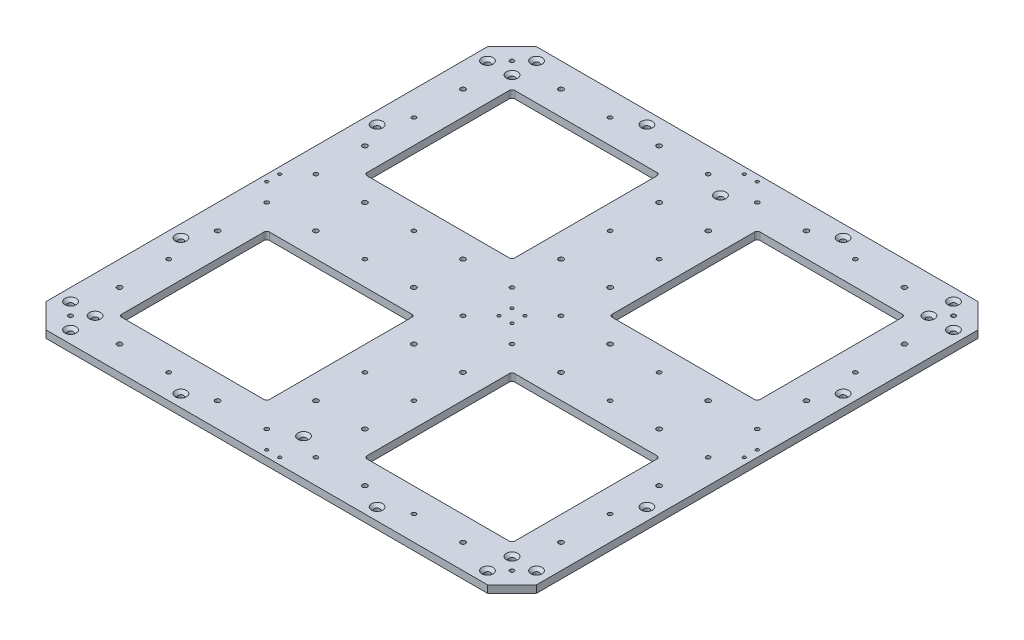
SolidWorks part; units mm, degrees
ref_plane "Front Plane" through (0, 0, 0) normal (0, 0, 1) x (1, 0, 0)
ref_plane "Top Plane" through (0, 0, 0) normal (0, 1, 0) x (1, 0, 0)
ref_plane "Right Plane" through (0, 0, 0) normal (1, 0, 0) x (0, 0, -1)
sketch "Sketch1" plane through (0, 0, 0) normal (0, 1, 0) x (1, 0, 0)
  line L0 (-400, 360) -> (-400, -360)
  line L1 (-400, -360) -> (-360, -400)
  line L2 (-360, -400) -> (360, -400)
  line L3 (360, -400) -> (400, -360)
  line L4 (400, -360) -> (400, 360)
  line L5 (400, 360) -> (360, 400)
  line L6 (360, 400) -> (-360, 400)
  line L7 (-360, 400) -> (-400, 360)
  line L8 (0, 400) -> (0, -400) construction
  line L9 (-400, 0) -> (400, 0) construction
  line L10 (-400, 360) -> (400, 360) construction
  line L11 (-400, -360) -> (400, -360) construction
  line L12 (-360, 400) -> (-360, -400) construction
  line L13 (360, -400) -> (360, 400) construction
  line L14 (-320.5, -79.5) -> (-320.5, 320.5) construction
  line L15 (-320.5, 320.5) -> (79.5, 320.5) construction
  line L16 (79.5, 79.5) -> (-320.5, 79.5) construction
  line L19 (-320.5, -79.5) -> (-79.5, -79.5)
  line L20 (-320.5, -79.5) -> (-320.5, -320.5)
  line L21 (-320.5, -320.5) -> (-79.5, -320.5)
  line L22 (-79.5, -79.5) -> (-79.5, -320.5)
  line L23 (79.5, 320.5) -> (320.5, 320.5)
  line L24 (79.5, 320.5) -> (79.5, 79.5)
  line L25 (79.5, 79.5) -> (320.5, 79.5)
  line L26 (320.5, 320.5) -> (320.5, 79.5)
  line L27 (79.5, -79.5) -> (320.5, -79.5)
  line L28 (79.5, -79.5) -> (79.5, -320.5)
  line L29 (79.5, -320.5) -> (320.5, -320.5)
  line L30 (320.5, -79.5) -> (320.5, -320.5)
  line L31 (-320.5, 320.5) -> (-79.5, 320.5)
  line L32 (-79.5, -320.5) -> (79.5, -320.5) construction
  line L33 (320.5, 79.5) -> (320.5, -79.5) construction
  line L34 (-320.5, 320.5) -> (-320.5, 79.5)
  line L35 (-320.5, 79.5) -> (-79.5, 79.5)
  line L36 (79.5, -79.5) -> (-79.5, -79.5) construction
  line L37 (79.5, 79.5) -> (79.5, -79.5) construction
  line L38 (-79.5, 320.5) -> (-79.5, 79.5)
  dimension "D1" = 800
  dimension "D2" = 800
  dimension "D3" = 40
  dimension "D4" = 79.5
  dimension "D5" = 79.5
  dimension "D6" = 79.5
  dimension "D7" = 79.5
  dimension "D8" = 79.5
  dimension "D9" = 79.5
  dimension "D10" = 79.5
  dimension "D11" = 79.5
extrude "Boss-Extrude1" add sketch "Sketch1" along normal blind 12
sketch "Sketch2" plane through (0, 12, 0) normal (0, 1, 0) x (1, 0, 0)
  line L0 (-400, 200) -> (-200, 200) construction
  line L1 (-400, 360) -> (-400, -360) construction
  line L2 (-200, 200) -> (-200, 400) construction
  line L3 (360, 400) -> (-360, 400) construction
  line L4 (-246.669, 153.331) -> (-153.331, 246.669) construction
  line L5 (-246.669, 246.669) -> (-153.331, 246.669) construction
  line L6 (-246.669, 246.669) -> (-246.669, 153.331) construction
  line L7 (-246.669, 153.331) -> (-153.331, 153.331) construction
  line L8 (-153.331, 246.669) -> (-153.331, 153.331) construction
  line L9 (-260, 210) -> (-140, 210) construction
  line L10 (-200, 200) -> (-200, 210) construction
  circle A0 centre (-200, 200) radius 74.5 construction
  circle A1 centre (-246.669, 153.331) radius 4.25
  circle A2 centre (-153.331, 153.331) radius 4.25
  circle A3 centre (-153.331, 246.669) radius 4.25
  circle A4 centre (-246.669, 246.669) radius 4.25
  circle A5 centre (-260, 210) radius 4
  circle A6 centre (-140, 210) radius 4
  dimension "D3" = 149
  dimension "D5" = 8.5
  dimension "D8" = 8
  dimension "D1" = 200
  dimension "D2" = 200
  dimension "D4" = 132
  dimension "D6" = 10
  dimension "D7" = 120
extrude "Cut-Extrude1" [suppressed] cut sketch "Sketch2" against normal through all
hole_wizard "M8 Tapped Hole1" positions "Sketch5" profile "Sketch6" tap size "M8" standard "ISO" end condition through all
sketch "Sketch5" plane through (0, 12, 0) normal (0, 1, 0) x (1, 0, 0)
  line L0 (-400, 360) -> (400, 360) construction
  line L2 (-360, 400) -> (-360, -400) construction
  line L4 (-400, -360) -> (400, -360) construction
  line L6 (360, -400) -> (360, 400) construction
  line L8 (-400, 0) -> (400, 0) construction
  line L9 (-400, 360) -> (-400, -360) construction
  line L10 (400, -360) -> (400, 360) construction
  line L12 (0, 400) -> (0, -400) construction
  line L13 (360, 400) -> (-360, 400) construction
  line L14 (-360, -400) -> (360, -400) construction
  line L16 (-400, -40) -> (400, -40) construction
  line L17 (-40, 400) -> (-40, -400) construction
  line L18 (-400, 40) -> (400, 40) construction
  line L19 (40, 400) -> (40, -400) construction
  line L21 (-200, 400) -> (-200, -400) construction
  line L22 (-400, -200) -> (400, -200) construction
  line L23 (200, 400) -> (200, -400) construction
  line L24 (-400, 200) -> (400, 200) construction
  point P47 (-360, 360)
  point P49 (360, 360)
  point P51 (-40, 360)
  point P53 (40, 360)
  point P55 (-40, 40)
  point P57 (40, 40)
  point P59 (360, 40)
  point P61 (-360, 40)
  point P63 (-360, -40)
  point P65 (-360, -360)
  point P67 (-40, -40)
  point P69 (-40, -360)
  point P71 (40, -360)
  point P73 (360, -360)
  point P75 (360, -40)
  point P77 (40, -40)
  point P90 (-200, 360)
  point P92 (200, 360)
  point P94 (360, 200)
  point P96 (200, 40)
  point P98 (40, 200)
  point P100 (-40, 200)
  point P102 (-200, 40)
  point P104 (-360, 200)
  point P106 (-200, -40)
  point P108 (-360, -200)
  point P110 (-200, -360)
  point P112 (-40, -200)
  point P114 (40, -200)
  point P116 (200, -40)
  point P118 (360, -200)
  point P120 (200, -360)
  dimension "D1" = 40
  dimension "D2" = 40
  dimension "D3" = 200
  dimension "D4" = 200
sketch "Sketch6" plane through (-360, 12, -360) normal (1, 0, 0) x (0, 0, 1)
  line L0 (0, 0) -> (0, 12)
  line L1 (0, 12) -> (3.4, 12)
  line L2 (3.4, 12) -> (3.4, 0)
  line L5 (3.4, 0) -> (0, 0)
  line L11 (0, -6.35) -> (0, 107.95) construction
  dimension "Thru Tap Drill Dia." = 6.8
  dimension "Thru Tap Drill Depth" = 12
cosmetic thread "Hole Thread1" parameters "D2"=8
cosmetic thread "Hole Thread2" parameters "D2"=8
cosmetic thread "Hole Thread3" parameters "D2"=8
cosmetic thread "Hole Thread4" parameters "D2"=8
cosmetic thread "Hole Thread5" parameters "D2"=8
cosmetic thread "Hole Thread6" parameters "D2"=8
cosmetic thread "Hole Thread7" parameters "D2"=8
cosmetic thread "Hole Thread8" parameters "D2"=8
cosmetic thread "Hole Thread9" parameters "D2"=8
cosmetic thread "Hole Thread10" parameters "D2"=8
cosmetic thread "Hole Thread11" parameters "D2"=8
cosmetic thread "Hole Thread12" parameters "D2"=8
cosmetic thread "Hole Thread13" parameters "D2"=8
cosmetic thread "Hole Thread14" parameters "D2"=8
cosmetic thread "Hole Thread15" parameters "D2"=8
cosmetic thread "Hole Thread16" parameters "D2"=8
cosmetic thread "Hole Thread17" parameters "D2"=8
cosmetic thread "Hole Thread18" parameters "D2"=8
cosmetic thread "Hole Thread19" parameters "D2"=8
cosmetic thread "Hole Thread20" parameters "D2"=8
cosmetic thread "Hole Thread21" parameters "D2"=8
cosmetic thread "Hole Thread22" parameters "D2"=8
cosmetic thread "Hole Thread23" parameters "D2"=8
cosmetic thread "Hole Thread24" parameters "D2"=8
cosmetic thread "Hole Thread25" parameters "D2"=8
cosmetic thread "Hole Thread26" parameters "D2"=8
cosmetic thread "Hole Thread27" parameters "D2"=8
cosmetic thread "Hole Thread28" parameters "D2"=8
cosmetic thread "Hole Thread29" parameters "D2"=8
cosmetic thread "Hole Thread30" parameters "D2"=8
cosmetic thread "Hole Thread31" parameters "D2"=8
cosmetic thread "Hole Thread32" parameters "D2"=8
hole_wizard "Ø8.0mm Dowel Hole1" positions "Sketch8" profile "Sketch7" hole size "Ø8.0" standard "ANSI Metric" end condition through all
sketch "Sketch8" plane through (0, 12, 0) normal (0, 1, 0) x (1, 0, 0)
  line L0 (-360, 360) -> (-200, 360) construction
  line L1 (-200, 360) -> (-40, 360) construction
  line L2 (-40, 360) -> (-40, 200) construction
  line L3 (-40, 200) -> (-40, 40) construction
  line L4 (-40, 40) -> (-200, 40) construction
  line L5 (-200, 40) -> (-360, 40) construction
  line L6 (-360, 40) -> (-360, 200) construction
  line L7 (-360, 200) -> (-360, 360) construction
  point P0 (-280, 360)
  point P2 (-120, 360)
  point P4 (-40, 280)
  point P6 (-40, 120)
  point P8 (-120, 40)
  point P10 (-280, 40)
  point P12 (-360, 120)
  point P14 (-360, 280)
sketch "Sketch7" plane through (-280, 12, -360) normal (1, 0, 0) x (0, 0, 1)
  line L0 (0, 0) -> (0, 12)
  line L1 (0, 12) -> (4, 12)
  line L2 (4, 12) -> (4, 0)
  line L5 (4, 0) -> (0, 0)
  line L11 (0, -6.35) -> (0, 107.95) construction
  dimension "Thru Hole Dia." = 8
  dimension "Thru Hole Depth" = 12
pattern_linear "LPattern1" count 2 spacing 400 along (1, 0, 0) count 2 spacing 400 along (0, 0, 1) of "Ø8.0mm Dowel Hole1"
hole_wizard "CSK for M8 Hex Socket Countersunk Head Screw1" positions "Sketch10" profile "Sketch9" countersink size "M8" standard "DIN" end condition through all
sketch "Sketch10" plane through (0, 12, 0) normal (0, 1, 0) x (1, 0, 0)
  line L0 (-380, 340) -> (-380, -340) construction
  line L1 (-380, -340) -> (380, -340) construction
  line L2 (380, -340) -> (380, 340) construction
  line L3 (380, 340) -> (-380, 340) construction
  line L5 (-340, 380) -> (-340, -380) construction
  line L6 (-340, -380) -> (340, -380) construction
  line L7 (340, -380) -> (340, 380) construction
  line L8 (340, 380) -> (-340, 380) construction
  line L10 (360, 400) -> (-360, 400) construction
  line L11 (-400, 360) -> (-400, -360) construction
  line L12 (400, -360) -> (400, 360) construction
  line L13 (-360, -400) -> (360, -400) construction
  line L14 (-160, 380) -> (-160, -380) construction
  line L16 (-380, 160) -> (380, 160) construction
  line L18 (-380, -160) -> (380, -160) construction
  line L20 (160, 380) -> (160, -380) construction
  point P0 (-380, 340)
  point P2 (-340, 380)
  point P6 (-380, -340)
  point P8 (380, -340)
  point P10 (380, 340)
  point P16 (-340, -380)
  point P17 (340, -380)
  point P19 (340, 380)
  point P52 (340, 340)
  point P54 (340, -340)
  point P56 (-340, -340)
  point P58 (0, -340)
  point P60 (0, 340)
  point P62 (-340, 340)
  point P64 (-160, 380)
  point P68 (160, 380)
  point P72 (380, 160)
  point P78 (380, -160)
  point P80 (160, -380)
  point P84 (-160, -380)
  point P88 (-380, -160)
  point P90 (-380, 160)
  dimension "D1" = 60
  dimension "D2" = 60
  dimension "D3" = 60
  dimension "D4" = 20
  dimension "D5" = 60
  dimension "D6" = 20
  dimension "D7" = 20
  dimension "D8" = 20
  dimension "D9" = 180
  dimension "D10" = 180
  dimension "D11" = 180
  dimension "D12" = 180
sketch "Sketch9" plane through (-380, 12, -340) normal (1, 0, 0) x (0, 0, 1)
  line L0 (0, 0) -> (0, 12)
  line L1 (0, 12) -> (4.5, 12)
  line L2 (4.5, 12) -> (4.5, 4.625)
  line L3 (4.5, 4.625) -> (9.125, 0)
  line L5 (9.125, 0) -> (0, 0)
  line L6 (-4.5, 4.625) -> (-9.125, 0) construction
  line L11 (0, -6.35) -> (0, 107.95) construction
  dimension "Thru Hole Dia." = 9
  dimension "Thru Hole Depth" = 12
  dimension "Near C'Sink Dia." = 18.25
  dimension "Near C'Sink Angle" = 90
fillet "Fillet1" radius 4.5 16 edges at (320.5, 6, -320.5) (-79.5, 6, 79.5) (320.5, 6, 79.5) (320.5, 6, -79.5) (320.5, 6, 320.5) (-79.5, 6, 320.5) (-320.5, 6, 79.5) (79.5, 6, 79.5) (79.5, 6, -320.5) (79.5, 6, -79.5) (79.5, 6, 320.5) (-320.5, 6, 320.5) (-320.5, 6, -79.5) (-79.5, 6, -79.5) (-79.5, 6, -320.5) (-320.5, 6, -320.5)
hole_wizard "M6 Tapped Hole1" positions "Sketch13" profile "Sketch12" tap size "M6" standard "ISO" end condition through all
sketch "Sketch13" plane through (0, 12, 0) normal (0, 1, 0) x (1, 0, 0)
  line L0 (0, 0) -> (-40, 0) construction
  line L1 (-40, 0) -> (0, 40) construction
  line L2 (0, 40) -> (0, 0) construction
  line L3 (0, 0) -> (0, -40) construction
  line L4 (0, -40) -> (-40, 0) construction
  line L6 (0, 0) -> (-20, -20) construction
  line L8 (0, 0) -> (-20, 20) construction
  line L9 (-400, 0) -> (-400, 40) construction
  line L11 (-400, 40) -> (-360, 0) construction
  line L12 (-360, 0) -> (-400, 0) construction
  line L13 (-400, 0) -> (-400, -40) construction
  line L14 (-400, -40) -> (-360, 0) construction
  line L16 (-400, 0) -> (-380, 20) construction
  line L18 (-400, 0) -> (-380, -20) construction
  line L19 (-400, 40) -> (0, 40) construction
  line L21 (-400, -40) -> (0, -40) construction
  line L22 (0, 0) -> (-360, 0) construction
  point P26 (-10.6066, 10.6066)
  point P28 (-10.6066, -10.6066)
  point P63 (-389.3934, 10.6066)
  point P65 (-389.3934, -10.6066)
  dimension "D1" = 40
  dimension "D2" = 40
  dimension "D3" = 15
  dimension "D4" = 15
  dimension "D5" = 400
  dimension "D6" = 15
  dimension "D7" = 15
sketch "Sketch12" plane through (-10.6066, 12, -10.6066) normal (1, 0, 0) x (0, 0, 1)
  line L0 (0, 0) -> (0, 12)
  line L1 (0, 12) -> (2.5, 12)
  line L2 (2.5, 12) -> (2.5, 0)
  line L5 (2.5, 0) -> (0, 0)
  line L11 (0, -6.35) -> (0, 107.95) construction
  dimension "Thru Tap Drill Dia." = 5
  dimension "Thru Tap Drill Depth" = 12
cosmetic thread "Hole Thread33" parameters "D2"=6
cosmetic thread "Hole Thread34" parameters "D2"=6
cosmetic thread "Hole Thread35" parameters "D2"=6
cosmetic thread "Hole Thread36" parameters "D2"=6
ref_axis "Axis1" through (0, 12.6, 0) along (0, -1, 0)
pattern_circular "CirPattern1" count 4 over 360 about axis through (0, 12.6, 0) along (0, -1, 0) of "M6 Tapped Hole1"
